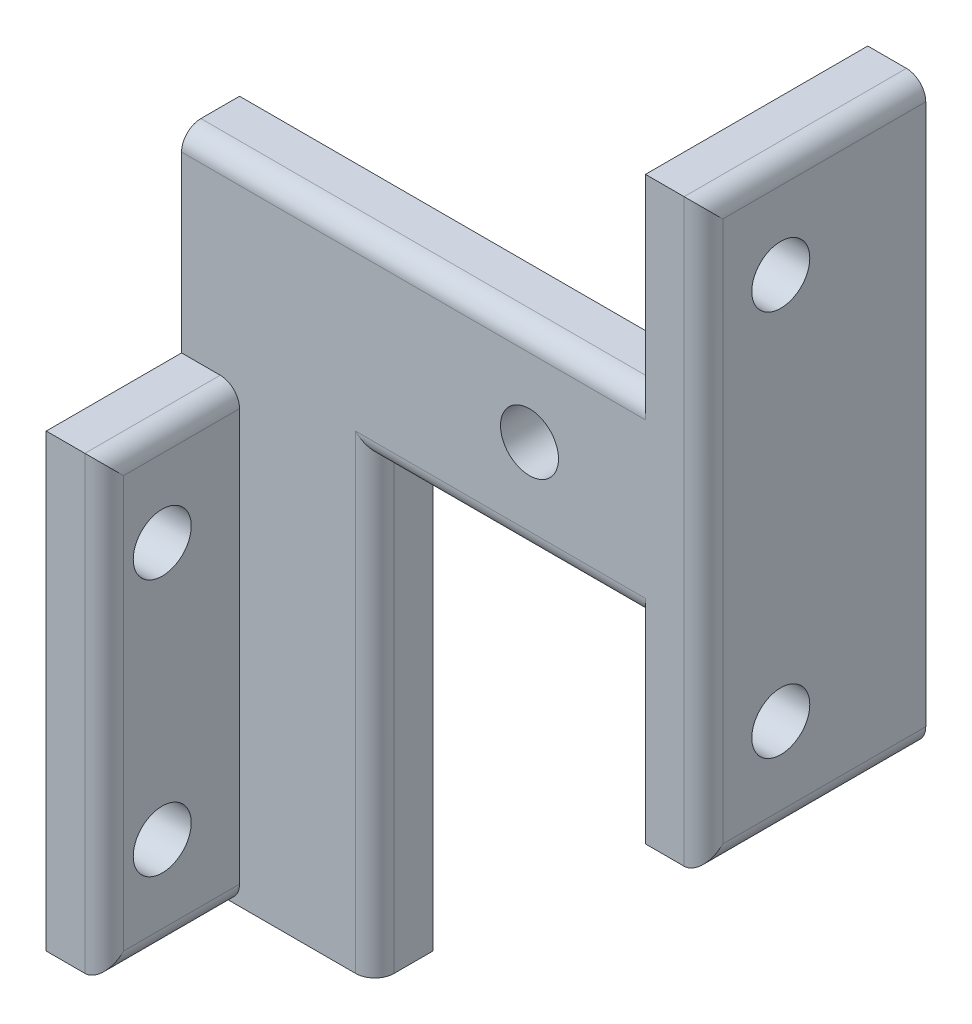
SolidWorks part; units mm, degrees
ref_plane "Alzado" through (0, 0, 0) normal (0, 0, 1) x (1, 0, 0)
ref_plane "Planta" through (0, 0, 0) normal (0, 1, 0) x (1, 0, 0)
ref_plane "Vista lateral" through (0, 0, 0) normal (1, 0, 0) x (0, 0, -1)
sketch "Croquis1" plane through (0, 0, 0) normal (1, 0, 0) x (0, 0, -1)
  line L1 (-23, 0) -> (0, 0)
  line L2 (-23, 0) -> (-23, -33.3)
  line L3 (-23, -33.3) -> (0, -33.3)
  line L4 (0, 0) -> (0, -33.3)
  dimension "D1" = 33.3
  dimension "D2" = 23
extrude "Saliente-Extruir2" add sketch "Croquis1" along normal blind 7
sketch "Croquis3" plane through (0, 0, 0) normal (0, 1, 0) x (1, 0, 0)
  line L0 (7, 0) -> (7, -23) construction
  line L1 (7, -1) -> (3, -1)
  line L2 (7, -1) -> (7, -20)
  line L3 (7, -20) -> (3, -20)
  line L4 (3, -1) -> (3, -20)
  line L5 (7, 0) -> (0, 0) construction
  line L6 (7, -23) -> (0, -23) construction
  line L7 (0, 0) -> (0, -23) construction
  dimension "D1" = 1
  dimension "D2" = 3
  dimension "D3" = 3
extrude "Cortar-Extruir1" cut sketch "Croquis3" against normal through all
sketch "Croquis7" plane through (0, 0, 0) normal (-1, 0, 0) x (0, 0, 1)
  line L0 (23, -33.3) -> (0, -33.3) construction
  line L1 (-7, 15) -> (30, 15)
  line L2 (-7, 15) -> (-7, -44.3)
  line L3 (-7, -44.3) -> (30, -44.3)
  line L4 (30, 15) -> (30, -44.3)
  line L5 (0, 0) -> (23, 0) construction
  line L6 (23, 0) -> (23, -33.3) construction
  line L7 (0, -33.3) -> (0, 0) construction
  line L9 (-7, 15) -> (0, 15)
  line L10 (-7, 15) -> (-7, 0)
  line L11 (-7, 0) -> (0, 0)
  line L12 (0, 15) -> (0, 0)
  line L13 (23, 0) -> (30, 0)
  line L14 (23, 0) -> (23, 15)
  line L15 (23, 15) -> (30, 15)
  line L16 (30, 0) -> (30, 15)
  line L17 (23, -33.3) -> (30, -33.3)
  line L18 (23, -33.3) -> (23, -44.3)
  line L19 (23, -44.3) -> (30, -44.3)
  line L20 (30, -33.3) -> (30, -44.3)
  line L21 (0, -33.3) -> (-7, -33.3)
  line L22 (0, -33.3) -> (0, -44.3)
  line L23 (0, -44.3) -> (-7, -44.3)
  line L24 (-7, -33.3) -> (-7, -44.3)
  circle A0 centre (-4, -15) radius 1.5
  circle A1 centre (-4, -28.3) radius 1.5
  circle A2 centre (27, -28.3) radius 1.5
  circle A3 centre (27, -15) radius 1.5
  circle A4 centre (4, 11) radius 1.5
  circle A5 centre (19, 11) radius 1.5
  circle A6 centre (4, -40.3) radius 1.5
  circle A7 centre (19, -40.3) radius 1.5
  dimension "D6" = 15
  dimension "D7" = 3
  dimension "D9" = 3
  dimension "D10" = 5
  dimension "D12" = 4
  dimension "D13" = 4
  dimension "D14" = 3
  dimension "D15" = 4
  dimension "D16" = 4
  dimension "D17" = 3
  dimension "D18" = 5
  dimension "D19" = 3
  dimension "D20" = 3
  dimension "D21" = 3
  dimension "D22" = 15
  dimension "D23" = 3
  dimension "D24" = 3
  dimension "D25" = 4
  dimension "D26" = 4
  dimension "D27" = 4
  dimension "D28" = 4
  dimension "D5" = 3
  dimension "D8" = 3
  dimension "D11" = 3
  dimension "D1" = 11
  dimension "D2" = 15
  dimension "D3" = 7
  dimension "D4" = 7
extrude "Saliente-Extruir3" add sketch "Croquis7" along normal blind 3 separate body
sketch "Croquis8" plane through (0, 0, 23) normal (0, 0, 1) x (1, 0, 0)
  line L1 (0, 0) -> (18, 0)
  line L2 (0, 0) -> (0, -10)
  line L3 (0, -10) -> (18, -10)
  line L4 (18, 0) -> (18, -10)
  circle A1 centre (15, -5) radius 1.5
  circle A2 centre (3, -5) radius 1.5
  dimension "D3" = 12
  dimension "D2" = 3
  dimension "D5" = 3
  dimension "D6" = 5
  dimension "D4" = 3
  dimension "D7" = 5
  dimension "D1" = 10
  dimension "D8" = 3
extrude "Saliente-Extruir5" add sketch "Croquis8" against normal blind 3
sketch "Croquis9" plane through (0, 0, 0) normal (0, 0, -1) x (-1, 0, 0)
  line L1 (0, 0) -> (-18, 0)
  line L2 (0, 0) -> (0, -10)
  line L3 (0, -10) -> (-18, -10)
  line L4 (-18, 0) -> (-18, -10)
  circle A1 centre (-15, -5) radius 1.5
  dimension "D1" = 3
extrude "Saliente-Extruir6" add sketch "Croquis9" against normal blind 1
sketch "Croquis10" plane through (18, 0, 0) normal (1, 0, 0) x (0, 0, -1)
  line L1 (-23, 0) -> (0, 0)
  line L2 (-23, 0) -> (-23, -10)
  line L3 (-23, -10) -> (0, -10)
  line L4 (0, 0) -> (0, -10)
extrude "Saliente-Extruir7" add sketch "Croquis10" along normal blind 3
sketch "Croquis11" plane through (3, 0, 0) normal (1, 0, 0) x (0, 0, -1)
  line L1 (-20, 0) -> (-1, 0)
  line L2 (-20, 0) -> (-20, -38)
  line L3 (-20, -38) -> (-1, -38)
  line L4 (-1, 0) -> (-1, -38)
  dimension "D1" = 38
  dimension "D2" = 19
extrude "Cortar-Extruir5" cut sketch "Croquis11" against normal through all
sketch "Croquis15" plane through (0, 0, 0) normal (1, 0, 0) x (0, 0, -1)
  line L1 (-30, 0) -> (-23, 0)
  line L2 (-30, 0) -> (-30, -10)
  line L3 (-30, -10) -> (-23, -10)
  line L4 (-23, 0) -> (-23, -10)
  line L5 (0, 0) -> (7, 0)
  line L6 (0, 0) -> (0, -10)
  line L7 (0, -10) -> (7, -10)
  line L8 (7, 0) -> (7, -10)
  line L9 (-30, 0) -> (-30, -33.3) construction
  line L10 (-23, 0) -> (-30, 0) construction
  dimension "D1" = 7
  dimension "D2" = 7
  dimension "D3" = 90
extrude "Cortar-Extruir8" cut sketch "Croquis15" against normal through all
sketch "Croquis16" plane through (0, 0, 0) normal (0, 0, -1) x (-1, 0, 0)
  line L0 (-7, -33.3) -> (-7, -10) construction
  line L1 (-7, -17.3) -> (0, -17.3)
  line L2 (-7, -17.3) -> (-7, -33.3)
  line L3 (-7, -33.3) -> (0, -33.3)
  line L4 (0, -17.3) -> (0, -33.3)
  line L5 (0, -33.3) -> (0, -10) construction
  line L6 (-7, -25.3) -> (0, -25.3) construction
  line L7 (-7, -33.3) -> (0, -33.3) construction
  dimension "D1" = 8
  dimension "D2" = 8
extrude "Cortar-Extruir9" cut sketch "Croquis16" against normal blind 1
sketch "Croquis18" plane through (21, 0, 0) normal (1, 0, 0) x (0, 0, -1)
  line L0 (0, -17.3) -> (0, -10) construction
  line L1 (-23, -10) -> (0, -10)
  line L2 (-23, -10) -> (-23, -20)
  line L3 (-23, -20) -> (0, -20)
  line L4 (0, -10) -> (0, -20)
  line L6 (-23, -10) -> (0, -10)
  line L7 (-23, -10) -> (-23, 10)
  line L8 (-23, 10) -> (0, 10)
  line L9 (0, -10) -> (0, 10)
  circle A0 centre (-19, 5) radius 1.5
  circle A1 centre (-4, 5) radius 1.5
  circle A2 centre (-19, -15) radius 1.5
  circle A3 centre (-4, -15) radius 1.5
  line M9 (-23, 0) -> (-23, -10)
  line M10 (-23, -10) -> (0, -10)
  line M11 (0, -10) -> (0, 0)
  line M12 (0, 0) -> (-23, 0)
  dimension "D4" = 3
  dimension "D5" = 3
  dimension "D6" = 4
  dimension "D7" = 5
  dimension "D8" = 5
  dimension "D9" = 4
  dimension "D10" = 3
  dimension "D11" = 3
  dimension "D12" = 4
  dimension "D13" = 4
  dimension "D14" = 5
  dimension "D15" = 5
  dimension "D2" = 10
  dimension "D3" = 23
  dimension "D16" = 20
  dimension "D17" = 90
extrude "Saliente-Extruir8" add sketch "Croquis18" along normal blind 3 contours L9 L8 L7 A1 A0 M12 | M12 M9 M10 M11 | L4 L2 L3 A3 A2 M10
fillet "Redondeo1" radius 1 19 edges at (0, -21.65, 30) (0, -10, 26.5) (0, -21.65, -7) (0, -10, -3.5) (24, -5, 23) (24, 10, 11.5) (24, -20, 11.5) (24, -5, 0) (7, -21.65, 23) (0, -38.8, 0) (0, -44.3, 11.5) (0, -33.3, 26.5) (0, -33.3, -3.5)
sketch "Croquis19" plane through (0, -44.3, 0) normal (0, -1, 0) x (-1, 0, 0)
  line L0 (3, -11.5) -> (-24, -11.5)
  line L1 (3, 0) -> (3, -23) construction
  line L2 (3, 7) -> (1, 7) construction
  line L3 (3, -11.5) -> (-24, -11.5)
  line L4 (3, -11.5) -> (3, 7)
  line L5 (3, 7) -> (-24, 7)
  line L6 (-24, -11.5) -> (-24, 7)
  line L7 (-24, -22) -> (-24, -1) construction
  line M3 (3, 0) -> (1, 0)
  line M4 (1, 0) -> (1, -23)
  line M6 (3, -23) -> (3, 0)
  dimension "D1" = 0
  dimension "D2" = 0
extrude "Cortar-Extruir10" cut sketch "Croquis19" against normal through all contours L6 L0 L4 L5 M4 M3 | L0 M6 M3 M4
sketch "Croquis20" plane through (24, 0, 0) normal (1, 0, 0) x (0, 0, -1)
  line L1 (-11.5, -44.3) -> (-23, -44.3)
  line L2 (-11.5, -44.3) -> (-11.5, -33.3)
  line L3 (-11.5, -33.3) -> (-23, -33.3)
  line L4 (-23, -44.3) -> (-23, -33.3)
extrude "Cortar-Extruir11" cut sketch "Croquis20" against normal through all
